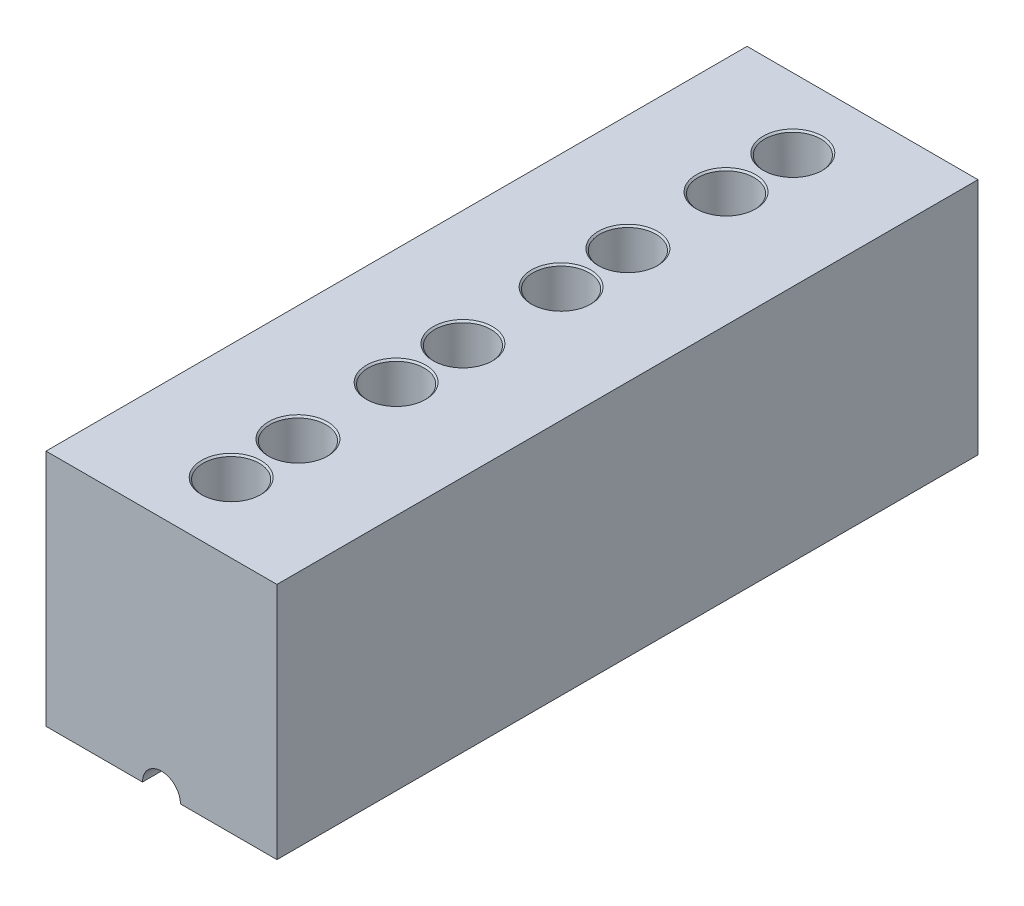
SolidWorks part; units mm, degrees
note: The reader was unsure of these and kept them because the rebuilt part matched: shared geometry of "Sketch9<4>".
ref_plane "Front Plane" through (0, 0, 0) normal (0, 0, 1) x (1, 0, 0)
ref_plane "Top Plane" through (0, 0, 0) normal (0, 1, 0) x (1, 0, 0)
ref_plane "Right Plane" through (0, 0, 0) normal (1, 0, 0) x (0, 0, -1)
sketch "Sketch1" plane through (0, 0, 0) normal (0, 1, 0) x (1, 0, 0)
  line L1 (-70, -212.5) -> (70, -212.5)
  line L2 (-70, -212.5) -> (-70, 212.5)
  line L3 (-70, 212.5) -> (70, 212.5)
  line L4 (70, -212.5) -> (70, 212.5)
  line L5 (0, 212.5) -> (0, -212.5) construction
  line L6 (-70, 0) -> (70, 0) construction
  point P0 (0, 0)
  dimension "D1" = 425
  dimension "D2" = 140
extrude "Boss-Extrude1" add sketch "Sketch1" along normal blind 150
sketch "Sketch6" plane through (0, 0, 0) normal (0, -1, 0) x (1, 0, 0)
  line L14 (-60, -202.5) -> (60, -202.5)
  line L15 (60, -202.5) -> (60, 202.5)
  line L16 (-60, 202.5) -> (-60, -202.5)
  line L17 (60, 202.5) -> (-60, 202.5)
  line L18 (-60, -202.5) -> (60, -202.5)
  line L19 (60, -202.5) -> (60, 202.5)
  line L20 (-60, 202.5) -> (-60, -202.5)
  line L21 (60, 202.5) -> (-60, 202.5)
  dimension "D1" = 10
extrude "Cut-Extrude1" cut sketch "Sketch6" against normal blind 80
sketch "Sketch7" plane through (0, 150, 0) normal (0, 1, 0) x (1, 0, 0)
  line L0 (0, -9.5) -> (0, 9.5) construction
  line L1 (0, -9.5) -> (0, -50) construction
  line L2 (0, 9.5) -> (0, 50) construction
  line L3 (0, -50) -> (0, -150) construction
  line L4 (0, 50) -> (0, 150) construction
  line L5 (0, 109.5) -> (0, 190.5) construction
  line L6 (0, 129.75) -> (0, 170.25)
  circle A0 centre (0, -50) radius 40.5
  circle A1 centre (0, 50) radius 40.5
  circle A2 centre (0, -150) radius 40.5
  circle A3 centre (0, 150) radius 40.5
  circle A4 centre (0, 170.25) radius 18
  circle A5 centre (0, 129.75) radius 18
  circle A6 centre (0, 29.75) radius 18
  circle A7 centre (0, 70.25) radius 18
  circle A8 centre (0, -70.25) radius 18
  circle A9 centre (0, -29.75) radius 18
  circle A10 centre (0, -170.25) radius 18
  circle A11 centre (0, -129.75) radius 18
  circle A12 centre (0, 170.25) radius 3
  circle A13 centre (0, 129.75) radius 3
  circle A14 centre (0, 70.25) radius 3
  circle A15 centre (0, 29.75) radius 3
  circle A16 centre (0, -29.75) radius 3
  circle A17 centre (0, -70.25) radius 3
  circle A18 centre (0, -129.75) radius 3
  circle A19 centre (0, -170.25) radius 3
  point P4 (0, 0)
  point P15 (0, 150)
  point P18 (0, 150)
  dimension "D6" = 81
  dimension "D7" = 81
  dimension "D9" = 36
  dimension "D10" = 36
  dimension "D12" = 6
  dimension "D13" = 6
  dimension "D1" = 19
  dimension "D2" = 40.5
  dimension "D3" = 40.5
  dimension "D4" = 100
  dimension "D5" = 100
  dimension "D8" = 40.5
  dimension "D11" = 4
  dimension "D14" = 4
sketch "Sketch8" plane through (-70, 0, 0) normal (-1, 0, 0) x (0, 0, 1)
  line L0 (-212.5, 150) -> (-212.5, 114.3071) construction
  line L1 (-212.5, 150) -> (-212.5, 0) construction
  line L2 (-212.5, 114.3071) -> (-188.25, 114.3071) construction
  line L3 (-188.25, 114.3071) -> (-152.25, 114.3071) construction
  line L4 (-170.25, 114.3071) -> (-170.25, 96.3071) construction
  line L5 (-170.25, 114.3071) -> (-170.25, 96.3071) construction
  line L6 (-152.25, 114.3071) -> (-152.25, 96.3071)
  line L7 (-188.25, 114.3071) -> (-188.25, 96.3071)
  line L8 (-88.25, 114.3071) -> (-88.25, 96.3071)
  line L9 (-52.25, 114.3071) -> (-52.25, 96.3071)
  line L10 (-70.25, 114.3071) -> (-70.25, 96.3071) construction
  line L11 (11.75, 114.3071) -> (11.75, 96.3071)
  line L12 (47.75, 114.3071) -> (47.75, 96.3071)
  line L13 (29.75, 114.3071) -> (29.75, 96.3071) construction
  line L14 (111.75, 114.3071) -> (111.75, 96.3071)
  line L15 (147.75, 114.3071) -> (147.75, 96.3071)
  line L16 (129.75, 114.3071) -> (129.75, 96.3071) construction
  line L17 (-170.25, 105.3071) -> (-129.75, 105.3071) construction
  line L18 (-129.75, 105.3071) -> (-129.75, 75.3071) construction
  line L19 (-129.75, 75.3071) -> (-129.75, 90.3071) construction
  line L20 (-147.75, 75.3071) -> (-147.75, 90.3071)
  line L21 (-111.75, 75.3071) -> (-111.75, 90.3071)
  line L22 (-11.75, 75.3071) -> (-11.75, 90.3071)
  line L23 (-47.75, 75.3071) -> (-47.75, 90.3071)
  line L24 (-29.75, 75.3071) -> (-29.75, 90.3071) construction
  line L25 (88.25, 75.3071) -> (88.25, 90.3071)
  line L26 (52.25, 75.3071) -> (52.25, 90.3071)
  line L27 (70.25, 75.3071) -> (70.25, 90.3071) construction
  line L28 (188.25, 75.3071) -> (188.25, 90.3071)
  line L29 (152.25, 75.3071) -> (152.25, 90.3071)
  line L30 (170.25, 75.3071) -> (170.25, 90.3071) construction
  arc A0 (-152.25, 114.3071) -> (-188.25, 114.3071) centre (-170.25, 114.3071) ccw
  arc A1 (-188.25, 96.3071) -> (-152.25, 96.3071) centre (-170.25, 96.3071) ccw
  arc A2 (-52.25, 114.3071) -> (-88.25, 114.3071) centre (-70.25, 114.3071) ccw
  arc A3 (-88.25, 96.3071) -> (-52.25, 96.3071) centre (-70.25, 96.3071) ccw
  arc A4 (47.75, 114.3071) -> (11.75, 114.3071) centre (29.75, 114.3071) ccw
  arc A5 (11.75, 96.3071) -> (47.75, 96.3071) centre (29.75, 96.3071) ccw
  arc A6 (147.75, 114.3071) -> (111.75, 114.3071) centre (129.75, 114.3071) ccw
  arc A7 (111.75, 96.3071) -> (147.75, 96.3071) centre (129.75, 96.3071) ccw
  arc A8 (-147.75, 75.3071) -> (-111.75, 75.3071) centre (-129.75, 75.3071) ccw
  arc A9 (-111.75, 90.3071) -> (-147.75, 90.3071) centre (-129.75, 90.3071) ccw
  arc A10 (-47.75, 75.3071) -> (-11.75, 75.3071) centre (-29.75, 75.3071) ccw
  arc A11 (-11.75, 90.3071) -> (-47.75, 90.3071) centre (-29.75, 90.3071) ccw
  arc A12 (52.25, 75.3071) -> (88.25, 75.3071) centre (70.25, 75.3071) ccw
  arc A13 (88.25, 90.3071) -> (52.25, 90.3071) centre (70.25, 90.3071) ccw
  arc A14 (152.25, 75.3071) -> (188.25, 75.3071) centre (170.25, 75.3071) ccw
  arc A15 (188.25, 90.3071) -> (152.25, 90.3071) centre (170.25, 90.3071) ccw
  point P9 (-170.25, 105.3071)
  point P18 (-70.25, 105.3071)
  point P25 (29.75, 105.3071)
  point P32 (129.75, 105.3071)
  point P37 (-129.75, 82.8071)
  point P44 (-147.75, 82.8071)
  point P45 (-29.75, 82.8071)
  point P53 (70.25, 82.8071)
  point P60 (170.25, 82.8071)
  dimension "D1" = 35.6929
  dimension "D2" = 24.25
  dimension "D3" = 36
  dimension "D4" = 36
  dimension "D5" = 4
  dimension "D6" = 40.5
  dimension "D7" = 30
  dimension "D8" = 36
  dimension "D9" = 4
extrude "Cut-Extrude2" cut sketch "Sketch7" against normal blind 120
sketch "Sketch9" plane through (0, 150, 0) normal (0, 1, 0) x (1, 0, 0)
  circle A0 centre (0, 170.25) radius 17
  circle A1 centre (0, 129.75) radius 17
  circle A2 centre (0, 70.25) radius 17
  circle A3 centre (0, 29.75) radius 17
  circle A4 centre (0, -29.75) radius 17
  circle A5 centre (0, -70.25) radius 17
  circle A6 centre (0, -129.75) radius 17
  circle A7 centre (0, -170.25) radius 17
  circle M4 centre (0, 70.25) radius 3
  circle M5 centre (0, 29.75) radius 3
  circle M6 centre (0, -29.75) radius 3
  circle M7 centre (0, -70.25) radius 3
  circle M8 centre (0, -170.25) radius 3
  circle M9 centre (0, -129.75) radius 3
  circle M10 centre (0, 170.25) radius 3
  circle M11 centre (0, 129.75) radius 3
  dimension "D1" = 34
  dimension "D2" = 34
  dimension "D3" = 4
extrude "Cut-Extrude4" cut sketch "Sketch9" against normal blind 60 contours A7 M8 | A5 M7 | A3 M5 | A1 M11
extrude "Cut-Extrude5" cut sketch "Sketch9<4>" against normal blind 30 contours A6 M9 | A4 M6 | A2 M4 | A0 M10
sketch "Sketch9<4>" plane through (0, 150, 0) normal (0, 1, 0) x (1, 0, 0) same geometry as "Sketch9"
chamfer "Chamfer1" distance 1 angle 45 8 edges at (0, 150, -153.25) (0, 150, -112.75) (0, 150, -53.25) (0, 150, -12.75) (0, 150, 46.75) (0, 150, 87.25) (0, 150, 146.75) (0, 150, 187.25)
sketch "Sketch12" plane through (0, 80, 0) normal (0, -1, 0) x (1, 0, 0)
  circle A0 centre (0, 170.25) radius 13
  circle A1 centre (0, 129.75) radius 13
  circle A2 centre (0, 70.25) radius 13
  circle A3 centre (0, 29.75) radius 13
  circle A4 centre (0, -29.75) radius 13
  circle A5 centre (0, -70.25) radius 13
  circle A6 centre (0, -129.75) radius 13
  circle A7 centre (0, -170.25) radius 13
  dimension "D1" = 26
  dimension "D2" = 26
  dimension "D3" = 4
extrude "Cut-Extrude6" cut sketch "Sketch12" against normal blind 2
sketch "Sketch13" plane through (0, 80, 0) normal (0, -1, 0) x (1, 0, 0)
  line L0 (0, 143.75) -> (0, 156.25) construction
  line L1 (0, 156.25) -> (0, 150) construction
  line L2 (-20.25, 170.25) -> (-20.25, 129.75)
  line L3 (20.25, 170.25) -> (20.25, 129.75)
  line L4 (-20.25, 70.25) -> (-20.25, 29.75)
  line L5 (20.25, 70.25) -> (20.25, 29.75)
  line L6 (-20.25, -29.75) -> (-20.25, -70.25)
  line L7 (20.25, -29.75) -> (20.25, -70.25)
  line L8 (-20.25, -129.75) -> (-20.25, -170.25)
  line L9 (20.25, -129.75) -> (20.25, -170.25)
  circle A0 centre (0, 170.25) radius 14
  circle A1 centre (0, 129.75) radius 14
  circle A2 centre (0, 170.25) radius 20.25
  circle A3 centre (0, 129.75) radius 20.25
  circle A4 centre (0, 29.75) radius 20.25
  circle A5 centre (0, 70.25) radius 20.25
  circle A6 centre (0, 29.75) radius 14
  circle A7 centre (0, 70.25) radius 14
  circle A8 centre (0, -70.25) radius 20.25
  circle A9 centre (0, -29.75) radius 20.25
  circle A10 centre (0, -70.25) radius 14
  circle A11 centre (0, -29.75) radius 14
  circle A12 centre (0, -170.25) radius 20.25
  circle A13 centre (0, -129.75) radius 20.25
  circle A14 centre (0, -170.25) radius 14
  circle A15 centre (0, -129.75) radius 14
  dimension "D1" = 28
  dimension "D2" = 28
  dimension "D3" = 6.25
  dimension "D4" = 4
extrude "Boss-Extrude6" add sketch "Sketch13" along normal blind 46.51 contours A3 A1 | A3 A2 L2 | A2 A0 | A3 L3 A2 | A5 L4 A4 | A4 A6 | A5 A4 L5 | A5 A7 | A9 L6 A8 | A9 A8 L7 | A9 A11 | A8 A10 | A13 L8 A12 | A13 A12 L9 | A13 A15 | A12 A14
sketch "Sketch16" plane through (0, 0, 0) normal (0, -1, 0) x (1, 0, 0)
  line L1 (-60, -202.5) -> (60, -202.5)
  line L2 (-60, -202.5) -> (-60, 202.5)
  line L3 (-60, 202.5) -> (60, 202.5)
  line L4 (70, -212.5) -> (70, 212.5)
  line L5 (70, 212.5) -> (-70, 212.5)
  line L6 (-70, 212.5) -> (-70, -212.5)
  line L7 (-70, -212.5) -> (70, -212.5)
  line L8 (70, -212.5) -> (70, 212.5)
  line L9 (70, 212.5) -> (-70, 212.5)
  line L10 (-70, 212.5) -> (-70, -212.5)
  line L11 (-70, -212.5) -> (70, -212.5)
  line L12 (60, -202.5) -> (60, 202.5)
  dimension "D1" = 0
extrude "Boss-Extrude7" add sketch "Sketch16" along normal blind 48
sketch "Sketch18" plane through (0, 0, 212.5) normal (0, 0, 1) x (1, 0, 0)
  line L0 (0, -48) -> (0, 5.49)
  line L1 (70, -48) -> (-70, -48) construction
  circle A0 centre (0, 5.49) radius 11.5
  dimension "D2" = 23
  dimension "D1" = 53.49
sketch "Sketch19" plane through (0, 80, 0) normal (0, -1, 0) x (1, 0, 0)
  line L0 (0, 9.5) -> (0, -9.5) construction
  line L1 (0, -90.5) -> (0, -109.5) construction
  line L2 (0, 109.5) -> (0, 90.5) construction
  line L3 (0, 190.5) -> (0, 202.5) construction
  line L4 (60, 202.5) -> (-60, 202.5) construction
  line L5 (0, -190.5) -> (0, -202.5) construction
  line L6 (-60, -202.5) -> (60, -202.5) construction
  line L7 (60, -202.5) -> (60, 202.5) construction
  line L8 (-60, 90.5) -> (60, 90.5)
  line L9 (-60, 90.5) -> (-60, 109.5)
  line L10 (-60, 109.5) -> (60, 109.5)
  line L11 (60, 90.5) -> (60, 109.5)
  line L12 (0, 109.5) -> (0, 90.5) construction
  line L13 (-60, 100) -> (60, 100) construction
  line L14 (-20.25, 170.25) -> (-20.25, 202.5)
  line L15 (-60, -9.5) -> (60, -9.5)
  line L16 (-60, -9.5) -> (-60, 9.5)
  line L17 (-60, 9.5) -> (60, 9.5)
  line L18 (60, -9.5) -> (60, 9.5)
  line L19 (0, 9.5) -> (0, -9.5) construction
  line L20 (-60, 0) -> (60, 0) construction
  line L21 (-60, -109.5) -> (60, -109.5)
  line L22 (-60, -109.5) -> (-60, -90.5)
  line L23 (-60, -90.5) -> (60, -90.5)
  line L24 (60, -109.5) -> (60, -90.5)
  line L25 (0, -90.5) -> (0, -109.5) construction
  line L26 (-60, -100) -> (60, -100) construction
  line L27 (20.25, 170.25) -> (20.25, 202.5)
  line L28 (20.25, 129.75) -> (20.25, 70.25)
  line L29 (-20.25, 70.25) -> (-20.25, 129.75)
  line L30 (-20.25, 29.75) -> (-20.25, -29.75)
  line L31 (20.25, 29.75) -> (20.25, -29.75)
  line L32 (20.25, -70.25) -> (20.25, -129.75)
  line L33 (20.25, -129.75) -> (20.25, -170.25) construction
  line L34 (-20.25, -70.25) -> (-20.25, -129.75)
  line L35 (-20.25, -170.25) -> (-20.25, -202.5)
  line L36 (20.25, -170.25) -> (20.25, -202.5)
  line L37 (0, 190.5) -> (0, 200) construction
  line L38 (0, -190.5) -> (0, -200) construction
  line L40 (-60, 209.5) -> (60, 209.5)
  line L41 (-60, 209.5) -> (-60, 190.5)
  line L42 (-60, 190.5) -> (60, 190.5)
  line L43 (60, 209.5) -> (60, 190.5)
  line L44 (0, 190.5) -> (0, 209.5) construction
  line L45 (-60, 200) -> (60, 200) construction
  line L46 (-60, -209.5) -> (60, -209.5)
  line L47 (-60, -209.5) -> (-60, -190.5)
  line L48 (-60, -190.5) -> (60, -190.5)
  line L49 (60, -209.5) -> (60, -190.5)
  line L50 (0, -190.5) -> (0, -209.5) construction
  line L51 (-60, -200) -> (60, -200) construction
  arc A0 (-20.25, 29.75) -> (20.25, 29.75) centre (0, 29.75) ccw construction
  arc A1 (20.25, -29.75) -> (-20.25, -29.75) centre (0, -29.75) ccw construction
  arc A2 (-20.25, -70.25) -> (20.25, -70.25) centre (0, -70.25) ccw construction
  arc A3 (20.25, -129.75) -> (-20.25, -129.75) centre (0, -129.75) ccw construction
  arc A4 (-20.25, 129.75) -> (20.25, 129.75) centre (0, 129.75) ccw construction
  arc A5 (20.25, 70.25) -> (-20.25, 70.25) centre (0, 70.25) ccw construction
  arc A6 (20.25, 170.25) -> (-20.25, 170.25) centre (0, 170.25) ccw construction
  arc A7 (-20.25, -170.25) -> (20.25, -170.25) centre (0, -170.25) ccw construction
  point P38 (0, 100)
  point P44 (0, 0)
  point P48 (0, -100)
  dimension "D1" = 9.5
  dimension "D2" = 9.5
extrude "Boss-Extrude18" add sketch "Sketch19" along normal blind 128
sketch "Sketch22" plane through (0, -48, 0) normal (0, -1, 0) x (1, 0, 0)
  line L1 (-60, 190.5) -> (60, 190.5)
  line L2 (-60, 190.5) -> (-60, 109.5)
  line L3 (-60, 109.5) -> (60, 109.5)
  line L4 (60, 190.5) -> (60, 109.5)
  line L5 (-60, 90.5) -> (60, 90.5)
  line L6 (-60, 90.5) -> (-60, 9.5)
  line L7 (-60, 9.5) -> (60, 9.5)
  line L8 (60, 90.5) -> (60, 9.5)
  line L9 (-60, -9.5) -> (60, -9.5)
  line L10 (-60, -9.5) -> (-60, -90.5)
  line L11 (-60, -90.5) -> (60, -90.5)
  line L12 (60, -9.5) -> (60, -90.5)
  line L13 (-60, -109.5) -> (60, -109.5)
  line L14 (-60, -109.5) -> (-60, -190.5)
  line L15 (-60, -190.5) -> (60, -190.5)
  line L16 (60, -109.5) -> (60, -190.5)
extrude "Cut-Extrude9" cut sketch "Sketch22" against normal up to surface (81.49 mm away)
extrude "Cut-Extrude10" cut sketch "Sketch18" against normal up to surface (425 mm away) up to face at (0, 51, -212.5)
sketch "Sketch23" plane through (0, -48, 0) normal (0, -1, 0) x (1, 0, 0)
  line L8 (-70, -212.5) -> (70, -212.5)
  line L9 (70, -212.5) -> (70, 212.5)
  line L10 (70, 212.5) -> (-70, 212.5)
  line L11 (-70, 212.5) -> (-70, -212.5)
  line L12 (-70, -212.5) -> (70, -212.5)
  line L13 (70, -212.5) -> (70, 212.5)
  line L14 (70, 212.5) -> (-70, 212.5)
  line L15 (-70, 212.5) -> (-70, -212.5)
  line L23 (-60, -190.5) -> (60, -190.5) construction
  line L24 (-20.25, 190.5) -> (20.25, 190.5)
  line L25 (-20.25, 190.5) -> (-20.25, 212.5)
  line L26 (-20.25, 212.5) -> (20.25, 212.5)
  line L27 (20.25, 190.5) -> (20.25, 212.5)
  line L28 (-20.25, -190.5) -> (20.25, -190.5)
  line L29 (-20.25, -190.5) -> (-20.25, -212.5)
  line L30 (-20.25, -212.5) -> (20.25, -212.5)
  line L31 (20.25, -190.5) -> (20.25, -212.5)
  line L33 (-20.25, -190.5) -> (-70, -190.5)
  line L34 (-20.25, -190.5) -> (-20.25, -212.5)
  line L35 (-20.25, -212.5) -> (-70, -212.5)
  line L36 (-70, -190.5) -> (-70, -212.5)
  line L37 (20.25, -190.5) -> (70, -190.5)
  line L38 (20.25, -190.5) -> (20.25, -212.5)
  line L39 (20.25, -212.5) -> (70, -212.5)
  line L40 (70, -190.5) -> (70, -212.5)
  line L41 (20.25, 212.5) -> (70, 212.5)
  line L42 (20.25, 212.5) -> (20.25, 190.5)
  line L43 (20.25, 190.5) -> (70, 190.5)
  line L44 (70, 212.5) -> (70, 190.5)
  line L45 (-20.25, 212.5) -> (-70, 212.5)
  line L46 (-20.25, 212.5) -> (-20.25, 190.5)
  line L47 (-20.25, 190.5) -> (-70, 190.5)
  line L48 (-70, 212.5) -> (-70, 190.5)
  line L49 (-70, 190.5) -> (-60, 190.5)
  line L50 (-70, 190.5) -> (-70, -190.5)
  line L51 (-70, -190.5) -> (-60, -190.5)
  line L52 (-60, 190.5) -> (-60, -190.5)
  line L53 (60, -190.5) -> (70, -190.5)
  line L54 (60, -190.5) -> (60, 190.5)
  line L55 (60, 190.5) -> (70, 190.5)
  line L56 (70, -190.5) -> (70, 190.5)
  line M13 (-60, 190.5) -> (60, 190.5)
  line M14 (60, 190.5) -> (60, 109.5)
  line M16 (-60, 109.5) -> (-60, 190.5)
  line M17 (-60, 9.5) -> (-60, 90.5)
  line M19 (60, 90.5) -> (60, 9.5)
  line M22 (60, -9.5) -> (60, -90.5)
  line M24 (-60, -90.5) -> (-60, -9.5)
  line M26 (60, -109.5) -> (60, -190.5)
  line M27 (60, -190.5) -> (-60, -190.5)
  line M28 (-60, -190.5) -> (-60, -109.5)
  line M29 (-70, -212.5) -> (70, -212.5)
  line M30 (70, -212.5) -> (70, 212.5)
  line M31 (70, 212.5) -> (-70, 212.5)
  line M32 (-70, 212.5) -> (-70, -212.5)
  dimension "D1" = 0
extrude "Cut-Extrude11" cut sketch "Sketch23" against normal blind 53.49 contours L47 L25 L14 M13 M32 | L52 L47 L15 L33 M16 M28 M24 M17 | L43 L27 M13 M30 M31 | L54 L37 L13 L43 M26 M14 M19 M22 | L33 L15 L29 M27 M29 | L37 L31 M27 M29 M30
sketch "Sketch24" plane through (0, -48, 0) normal (0, -1, 0) x (1, 0, 0)
  line L1 (-60, -90.5) -> (60, -90.5)
  line L2 (-60, -90.5) -> (-60, -109.5)
  line L3 (-60, -109.5) -> (60, -109.5)
  line L4 (60, -90.5) -> (60, -109.5)
  line L5 (-60, 9.5) -> (60, 9.5)
  line L6 (-60, 9.5) -> (-60, -9.5)
  line L7 (-60, -9.5) -> (60, -9.5)
  line L8 (60, 9.5) -> (60, -9.5)
  line L9 (-60, 109.5) -> (60, 109.5)
  line L10 (-60, 109.5) -> (-60, 90.5)
  line L11 (-60, 90.5) -> (60, 90.5)
  line L12 (60, 109.5) -> (60, 90.5)
extrude "Cut-Extrude12" cut sketch "Sketch24" against normal up to surface (53.49 mm away) up to face at (-50.0714, 5.49, 0)
sketch "Sketch25" plane through (0, -48, 0) normal (0, -1, 0) x (1, 0, 0)
  line L1 (-20.25, -190.5) -> (20.25, -190.5)
  line L2 (-20.25, -190.5) -> (-20.25, -212.5)
  line L3 (-20.25, -212.5) -> (20.25, -212.5)
  line L4 (20.25, -190.5) -> (20.25, -212.5)
  line L5 (-20.25, 212.5) -> (20.25, 212.5)
  line L6 (-20.25, 212.5) -> (-20.25, 190.5)
  line L7 (-20.25, 190.5) -> (20.25, 190.5)
  line L8 (20.25, 212.5) -> (20.25, 190.5)
extrude "Cut-Extrude13" cut sketch "Sketch25" against normal up to surface (53.49 mm away) up to face at (-38.5, 5.49, 0)
